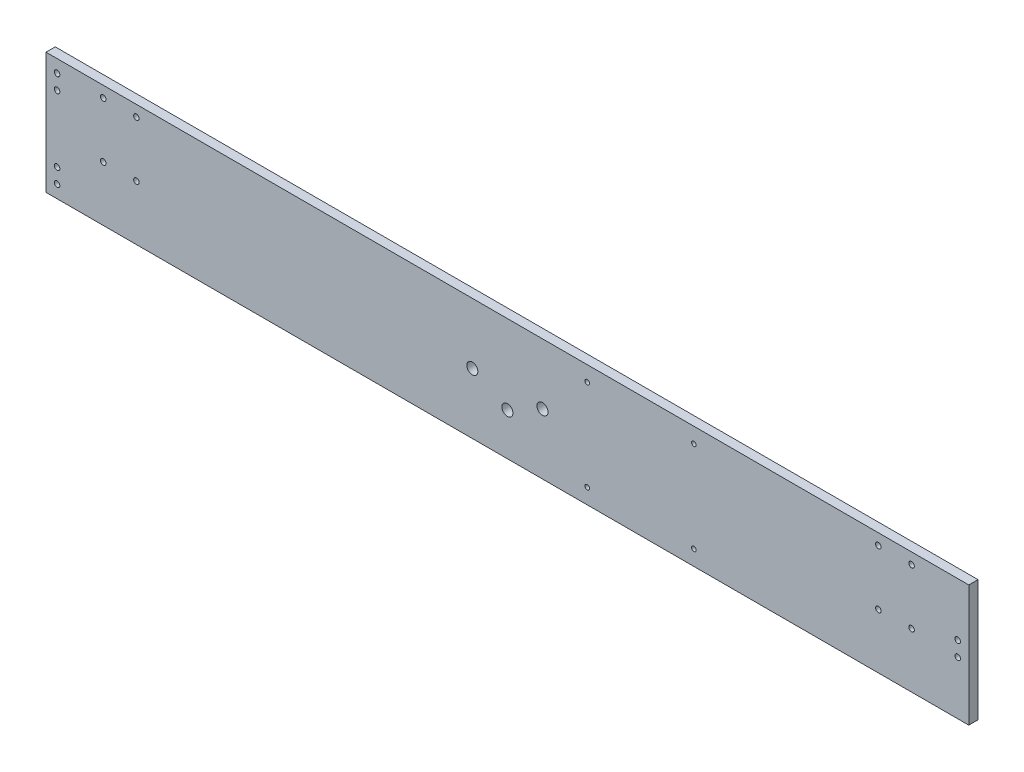
SolidWorks part; units mm, degrees
ref_plane "前视基准面" through (0, 0, 0) normal (0, 0, 1) x (1, 0, 0)
ref_plane "上视基准面" through (0, 0, 0) normal (0, 1, 0) x (1, 0, 0)
ref_plane "右视基准面" through (0, 0, 0) normal (1, 0, 0) x (0, 0, -1)
sketch "草图3" plane through (0, 0, 0) normal (0, 0, 1) x (1, 0, 0)
  line L1 (250, -32.9) -> (-250, -32.9)
  line L2 (250, -32.9) -> (250, 32.9)
  line L3 (250, 32.9) -> (-250, 32.9)
  line L4 (-250, -32.9) -> (-250, 32.9)
  line L5 (250, -32.9) -> (-250, 32.9) construction
  line L6 (250, 32.9) -> (-250, -32.9) construction
  line L7 (125, -27.9) -> (40, -27.9) construction
  line L8 (125, -27.9) -> (125, 27.9) construction
  line L9 (125, 27.9) -> (40, 27.9) construction
  line L10 (40, -27.9) -> (40, 27.9) construction
  line L11 (125, -27.9) -> (40, 27.9) construction
  line L12 (125, 27.9) -> (40, -27.9) construction
  line L13 (-30, -3) -> (-22.7964, -3) construction
  line L14 (-30, -3) -> (-30, 3) construction
  line L15 (-30, 3) -> (-22.7964, 3) construction
  circle A0 centre (43.25, 24.65) radius 1.25
  circle A1 centre (43.25, -24.65) radius 1.25
  circle A2 centre (101.05, -24.65) radius 1.25
  circle A3 centre (101.05, 24.65) radius 1.25
  point P0 (0, 0)
  point P6 (82.5, 0)
  point P19 (0, 0)
  dimension "D9" = 2.5
  dimension "D12" = 2.5
  dimension "D14" = 2.5
  dimension "D16" = 2.5
  dimension "D1" = 500
  dimension "D2" = 55.8
  dimension "D3" = 5
  dimension "D4" = 5
  dimension "D5" = 85
  dimension "D6" = 40
  dimension "D7" = 3.25
  dimension "D8" = 3.25
  dimension "D10" = 3.25
  dimension "D11" = 3.25
  dimension "D13" = 3.25
  dimension "D15" = 57.8
  dimension "D18" = 0
  dimension "D19" = 6
  dimension "D20" = 0
extrude "凸台-拉伸2" add sketch "草图3" along normal blind 5
sketch "草图4" plane through (0, 0, 5) normal (0, 0, 1) x (1, 0, 0)
  line L0 (-250, -32.9) -> (250, -32.9) construction
  line L1 (-210, 32.9) -> (-210, -32.9) construction
  line L2 (210, 32.9) -> (210, -32.9) construction
  line L3 (0, 32.9) -> (0, -32.9) construction
  line L4 (250, 32.9) -> (-250, 32.9) construction
  line L5 (250, -32.9) -> (250, 32.9) construction
  circle A0 centre (219, 26.9) radius 1.5
  circle A1 centre (219, -3.1) radius 1.5
  circle A2 centre (-219, -3.1) radius 1.5
  circle A3 centre (-219, 26.9) radius 1.5
  circle A4 centre (201, -3.1) radius 1.5
  circle A5 centre (201, 26.9) radius 1.5
  circle A6 centre (-201, -3.1) radius 1.5
  circle A7 centre (-201, 26.9) radius 1.5
  dimension "D1" = 3
  dimension "D2" = 3
  dimension "D3" = 40
  dimension "D4" = 30
  dimension "D5" = 6
  dimension "D6" = 18
extrude "切除-拉伸1" cut sketch "草图4" against normal blind 5
sketch "草图5" plane through (0, 0, 5) normal (0, 0, 1) x (1, 0, 0)
  line L0 (250, 32.9) -> (-250, 32.9) construction
  line L1 (-250, 32.9) -> (-250, -32.9) construction
  line L2 (-244, 26) -> (-244, 4) construction
  line L3 (-250, -32.9) -> (250, -32.9) construction
  line L4 (0, 32.9) -> (0, -32.9) construction
  line L5 (244, 26) -> (244, 4) construction
  circle A0 centre (-244, 26) radius 1.5
  circle A12 centre (-244, 18) radius 1.5
  circle A13 centre (-244, 4) radius 1.5
  circle A14 centre (-244, -4) radius 1.5
  circle A15 centre (-244, -18) radius 1.5
  circle A16 centre (-244, -26) radius 1.5
  circle A23 centre (244, -26) radius 1.5
  circle A24 centre (244, -18) radius 1.5
  circle A25 centre (244, -4) radius 1.5
  circle A26 centre (244, 4) radius 1.5
  circle A27 centre (244, 18) radius 1.5
  circle A28 centre (244, 26) radius 1.5
  dimension "D1" = 3
  dimension "D4" = 3
  dimension "D2" = 6.9
  dimension "D3" = 6
  dimension "D5" = 8
  dimension "D6" = 3
  dimension "D7" = 22
extrude "切除-拉伸2" cut sketch "草图5" against normal blind 5 contours A0 | A12 | A26 | A15 | A16 | A25 region at (-244, 26, 5) region at (-244, 18, 5) region at (-244, -18, 5) region at (-244, -26, 5) region at (244, -4, 5) region at (244, 4, 5)
sketch "草图6" plane through (0, 0, 5) normal (0, 0, 1) x (1, 0, 0)
  circle A0 centre (19, 0) radius 3
  circle A1 centre (-19, 0) radius 3
  circle A2 centre (0, -10) radius 3
  point P7 (0, 0)
  dimension "D3" = 6
  dimension "D4" = 6
  dimension "D5" = 6
  dimension "D1" = 19
  dimension "D2" = 19
  dimension "D6" = 10
extrude "切除-拉伸3" cut sketch "草图6" against normal blind 10
